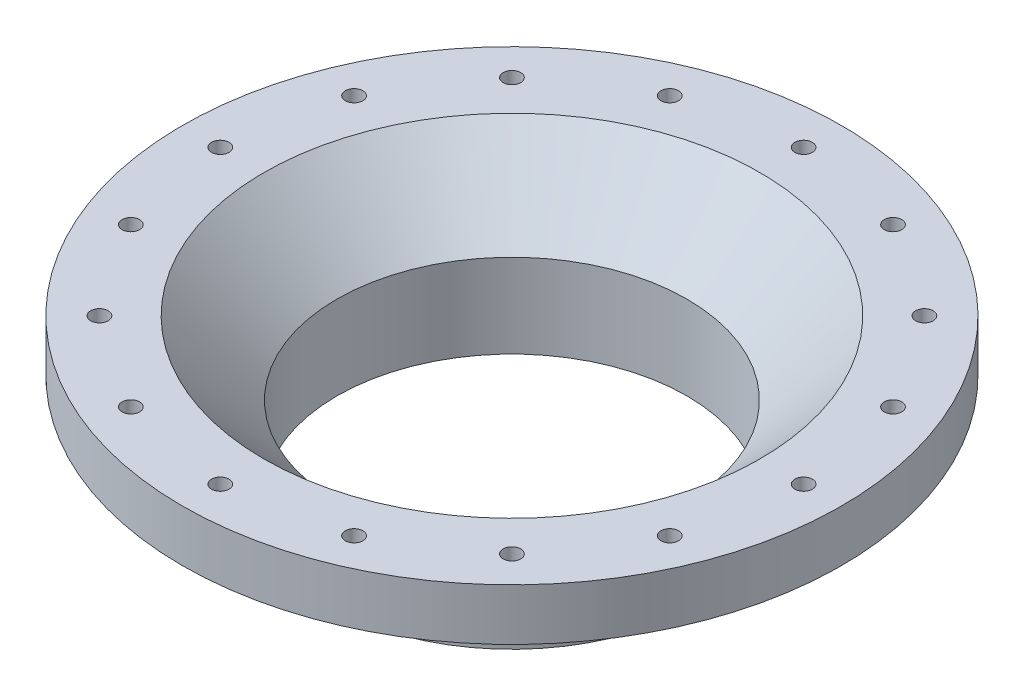
SolidWorks part; units mm, degrees
material "Stainless Steel 2205"
ref_plane "Front Plane" through (0, 0, 0) normal (0, 0, 1) x (1, 0, 0)
ref_plane "Top Plane" through (0, 0, 0) normal (0, 1, 0) x (1, 0, 0)
ref_plane "Right Plane" through (0, 0, 0) normal (1, 0, 0) x (0, 0, -1)
sketch "Sketch1" plane through (0, 0, 0) normal (0, 0, 1) x (1, 0, 0)
  line L0 (0, 0) -> (362.6143, 0) construction
  line L1 (425.2286, 62.6143) -> (300, -62.6143)
  line L2 (0, 21.0881) -> (0, -24.6757) construction
  line L3 (425.2286, 62.6143) -> (564.9629, 62.6143)
  line L4 (564.9629, 62.6143) -> (564.9629, -25.9357)
  line L5 (564.9629, -25.9357) -> (364.9629, -25.9357)
  line L8 (320, -206.3831) -> (300, -206.3831)
  line L9 (300, -206.3831) -> (300, -62.6143)
  line L10 (320, -206.3831) -> (320, -70.8986)
  line L11 (320, -22.4264) -> (324.8528, -17.5736)
  line L12 (320, -56.3831) -> (318.3333, -56.3831)
  line L13 (320, -104.0831) -> (318.3333, -104.0831)
  line L14 (320, -104.0831) -> (320, -106.3831)
  line L15 (320, -106.3831) -> (318.3333, -106.3831)
  line L16 (318.3333, -104.0831) -> (318.3333, -106.3831)
  line L17 (320, -54.0831) -> (320, -56.3831)
  line L18 (320, -54.0831) -> (318.3333, -54.0831)
  line L19 (318.3333, -54.0831) -> (318.3333, -56.3831)
  line L20 (320, -70.8986) -> (364.9629, -25.9357)
  point P10 (362.6143, 0)
  point P13 (362.6143, 0)
  dimension "D1" = 177.1
  dimension "D2" = 45
  dimension "D5" = 45
  dimension "D3" = 300
  dimension "D8" = 20
  dimension "D9" = 2.3
  dimension "D10" = 1.6667
  dimension "D11" = 100
  dimension "D13" = 47.7
  dimension "D14" = 88.55
  dimension "D15" = 20
  dimension "D4" = 200
  dimension "D12" = 2
revolve "Revolve1" add sketch "Sketch1" angle 360 about L2 region at (440.9713, -9.5552, 0)
sketch "Sketch2" plane through (0, 62.6143, 0) normal (0, 1, 0) x (1, 0, 0)
  line L0 (-147.9486, 0) -> (147.9486, 0) construction
  line L1 (0, -147.9486) -> (0, 147.9486) construction
  circle A1 centre (500, 0) radius 15
  circle A2 centre (0, 0) radius 425.2286 construction
  circle A3 centre (461.9398, -191.3417) radius 15
  circle A4 centre (353.5534, -353.5534) radius 15
  circle A5 centre (191.3417, -461.9398) radius 15
  circle A6 centre (0, -500) radius 15
  circle A7 centre (-191.3417, -461.9398) radius 15
  circle A8 centre (-353.5534, -353.5534) radius 15
  circle A9 centre (-461.9398, -191.3417) radius 15
  circle A10 centre (-500, 0) radius 15
  circle A11 centre (-461.9398, 191.3417) radius 15
  circle A12 centre (-353.5534, 353.5534) radius 15
  circle A13 centre (-191.3417, 461.9398) radius 15
  circle A14 centre (0, 500) radius 15
  circle A15 centre (191.3417, 461.9398) radius 15
  circle A16 centre (353.5534, 353.5534) radius 15
  circle A17 centre (461.9398, 191.3417) radius 15
  point P37 (0, 0)
  dimension "D3" = 30
  dimension "D1" = 500
  dimension "D4" = 500
  dimension "D2" = 16
extrude "Cut-Extrude2" cut sketch "Sketch2" against normal blind 130
fillet "Fillet1" radius 10 2 edges at (0, -70.8986, 320) (0, -25.9357, 364.9629)
sketch "Sketch3" plane through (0, 62.6143, 0) normal (0, 1, 0) x (1, 0, 0)
  line L0 (384.8528, 206.806) -> (384.8528, -202.504) construction
  line L1 (0, 0) -> (581.1839, 0) construction
  line L2 (434.8528, 80) -> (474.8528, 80)
  line L3 (434.8528, 80) -> (434.8528, 40)
  line L4 (434.8528, 40) -> (474.8528, 40)
  line L5 (474.8528, 80) -> (474.8528, 40)
  line L6 (434.8528, 80) -> (474.8528, 40) construction
  line L7 (434.8528, 40) -> (474.8528, 80) construction
  line L12 (434.8528, -40) -> (474.8528, -80) construction
  line L13 (434.8528, -80) -> (474.8528, -40) construction
  line L14 (474.8528, -80) -> (474.8528, -40)
  line L15 (434.8528, -80) -> (434.8528, -40)
  line L16 (434.8528, -80) -> (474.8528, -80)
  line L17 (434.8528, -40) -> (474.8528, -40)
  circle A1 centre (0, 0) radius 384.8528 construction
  point P4 (454.8528, 60)
  point P13 (454.8528, -60)
  dimension "D1" = 70
  dimension "D3" = 80
  dimension "D2" = 40
  dimension "D4" = 40
extrude "Boss-Extrude1" add sketch "Sketch3" along normal blind 60
sketch "Sketch4" plane through (0, 0, 80) normal (0, 0, 1) x (1, 0, 0)
  line L0 (434.8528, 62.6143) -> (474.8528, 62.6143) construction
  line L1 (434.8528, 122.6143) -> (434.8528, 62.6143) construction
  circle A0 centre (454.8528, 102.6143) radius 10
  dimension "D2" = 20
  dimension "D1" = 40
  dimension "D3" = 20
extrude "Cut-Extrude3" cut sketch "Sketch4" against normal blind 340
fillet "Fillet2" radius 20 4 edges at (474.8528, 122.6143, -60) (434.8528, 122.6143, -60) (434.8528, 122.6143, 60) (474.8528, 122.6143, 60)
fillet "Fillet3" radius 10 8 edges at (454.8528, 62.6143, 40) (434.8528, 62.6143, 60) (454.8528, 62.6143, 80) (474.8528, 62.6143, 60) (474.8528, 62.6143, -60) (454.8528, 62.6143, -80) (434.8528, 62.6143, -60) (454.8528, 62.6143, -40)
sketch "Sketch5" plane through (0, 0, 0) normal (1, 0, 0) x (0, 0, -1)
  line L1 (-564.9629, 62.6143) -> (564.9629, 62.6143)
  line L2 (-564.9629, 62.6143) -> (-564.9629, 175.245)
  line L3 (-564.9629, 175.245) -> (564.9629, 175.245)
  line L4 (564.9629, 62.6143) -> (564.9629, 175.245)
extrude "Cut-Extrude4" cut sketch "Sketch5" against normal through all both and the other way through all
sketch "Sketch7" plane through (0, 0, 0) normal (0, 0, 1) x (1, 0, 0)
  line L0 (0, -35.0965) -> (0, -106.1189) construction
  circle A0 centre (319.483, -85.0652) radius 1.1
  dimension "D1" = 2.2
revolve "Revolve2" add sketch "Sketch7" angle 360 about L0
equation "\"hatchHoleDiameter\"=600mm"
equation "\"hullThickness\"=177.1mm"
equation "\"gasketHullInterconnectWidth\"=100mm"
equation "\"collarThickness\"=20mm"
equation "\"D8@Sketch1\"=\"collarThickness\""
equation "\"hatchTunnelLength\"=200mm"
equation "\"oRingDiameter\"=2mm"
equation "\"D9@Sketch1\"=\"oRingDiameter\"+0.3"
equation "\"D10@Sketch1\"=\"oRingDiameter\"/1.2"
equation "\"D14@Sketch1\"=\"hullThickness\"/2"
equation "\"D1@Sketch1\"=\"hullThickness\""
equation "\"boltPatternRadiusInterconnect\"=500mm"
equation "\"D1@Sketch2\"=\"boltPatternRadiusInterconnect\""
equation "\"interconnectBoltDiameter\"=30mm"
equation "\"D3@Sketch2\"=\"interconnectBoltDiameter\""
equation "\"D4@Sketch2\"=\"boltPatternRadiusInterconnect\""
equation "\"hatchShaftDiameter\"=20mm"
equation "\"hatchMinima\"=39.9mm"
equation "\"hullDiameter\"=2240mm"
equation "\"hatchMaxima\"=180mm"
equation "\"bushingFlatHatch\"=15mm"
equation "\"hingePivotDiameter\"=20mm"
equation "\"handleWidth\"=250mm"
equation "\"handleHeight\"=160mm"
equation "\"handleThickness\"=25mm"
equation "\"D4@Sketch1\"=\"gasketHullInterconnectWidth\"*2"
equation "\"D6@Sketch1\"=\"gasketHullInterconnectWidth\"*2"
equation "\"D1@HatchTop1\"=\"hatchHoleDiameter\"/2"
equation "\"D4@HatchTop1\"=\"hatchShaftDiameter\"/2"
equation "\"D7@HatchTop1\"=\"bushingFlatHatch\""
equation "\"D11@HatchTop1\"=\"oRingDiameter\"*1.3"
equation "\"D12@HatchTop1\"=\"oRingDiameter\"/1.1"
equation "\"D13@HatchTop1\"=\"oRingDiameter\"*1.3"
equation "\"D14@HatchTop1\"=\"oRingDiameter\"/1.3"
equation "\"D16@HatchTop1\"=\"hatchMinima\"/2"
equation "\"D1@Hinge\"=\"hingePivotDiameter\""
equation "\"D2@Hinge\"=\"hingePivotDiameter\"*2"
equation "\"D1@Sketch6\"=\"handleWidth\""
equation "\"D2@Sketch6\"=\"handleHeight\""
equation "\"D1@Sketch8\"=\"handleThickness\""
equation "\"hatchTopToDogArmCenter\"=33mm"
equation "\"dogArmSize\"=30mm"
equation "\"D1@Sketch10\"=\"dogArmSize\" + 0.2"
equation "\"D2@Sketch10\"=\"hatchTopToDogArmCenter\""
equation "\"D1@Sketch12\"=\"dogArmSize\"+0.2"
equation "\"D2@Sketch12\"=\"hatchTopToDogArmCenter\""
equation "\"D10@HatchTop1\"=\"hullDiameter\"/2"
equation "\"D5@HatchTop1\"=\"hullDiameter\"/2 - \"hatchMinima\""
equation "\"hatchPivotHeight\"=40mm"
equation "\"hatchPivotDistance\"=70mm"
equation "\"D4@Hinge\"=\"hatchPivotDistance\""
equation "\"D21@HatchTop1\"=\"HatchORingDiameter\"*2 -0.2"
equation "\"HatchORingDiameter\"=2.1mm"
equation "\"D20@HatchTop1\"=\"HatchORingDiameter\"+0.1"
equation "\"D3@Hinge\"=\"hatchPivotHeight\""
equation "\"FrameLength\"=2600mm"
equation "\"FrameMidLength\"=1800mm"
equation "\"TubeOD\"=100mm"
equation "\"FrameBackFlat\"=500mm"
equation "\"TubeWall\"=15.0001mm"
equation "\"TopMemberAngle\"=140deg"
equation "\"D1@Sketch3\"=\"hatchPivotDistance\""
equation "\"D2@Sketch3\"=\"hingePivotDiameter\"*2"
equation "\"D4@Sketch3\"=\"hingePivotDiameter\"*2"
equation "\"D1@Boss-Extrude1\"=\"hatchPivotHeight\"+\"hingePivotDiameter\""
equation "\"D1@Sketch4\"=\"hatchPivotHeight\""
equation "\"D3@Sketch4\"=\"hingePivotDiameter\""
